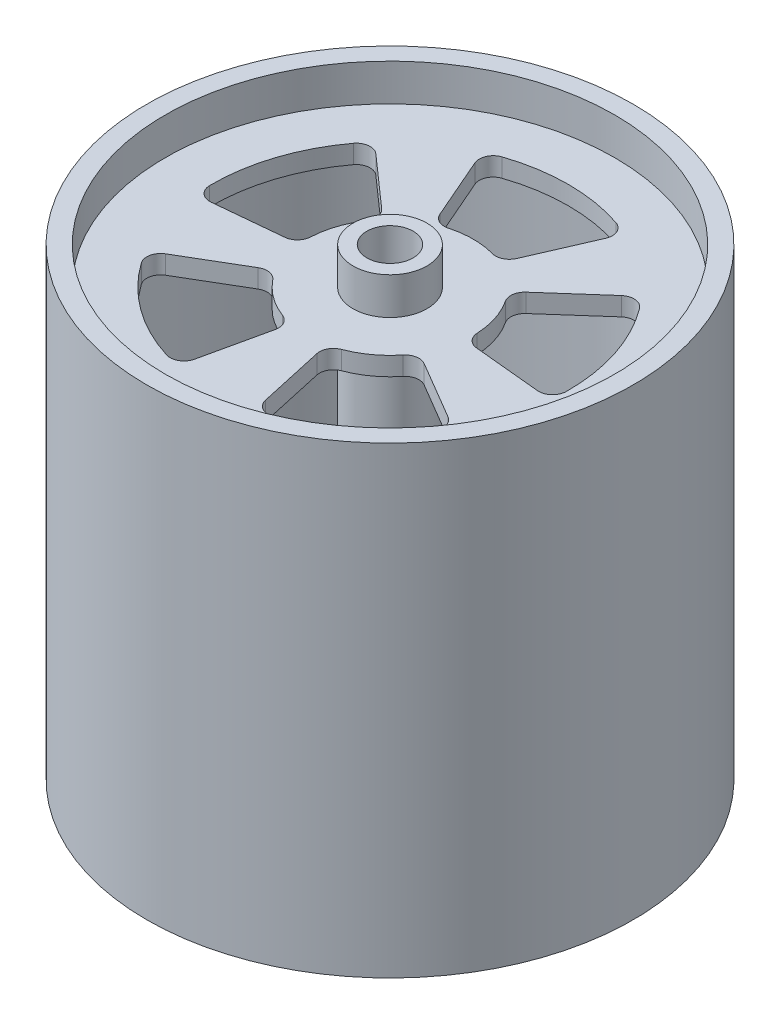
SolidWorks part; units mm, degrees
ref_plane "Front Plane" through (0, 0, 0) normal (0, 0, 1) x (1, 0, 0)
ref_plane "Top Plane" through (0, 0, 0) normal (0, 1, 0) x (1, 0, 0)
ref_plane "Right Plane" through (0, 0, 0) normal (1, 0, 0) x (0, 0, -1)
sketch "Sketch1" plane through (0, 0, 0) normal (0, 1, 0) x (1, 0, 0)
  circle A0 centre (0, 0) radius 52.5
  circle A1 centre (0, 0) radius 48.5
  dimension "D1" = 105
  dimension "D2" = 97
extrude "Boss-Extrude1" add sketch "Sketch1" along normal blind 100
sketch "Sketch2" plane through (0, 0, 0) normal (0, -1, 0) x (1, 0, 0)
  line L0 (7.6561, 34.5345) -> (4.4986, 20.2919)
  line L1 (7.6085, 2.4721) -> (46.1262, 14.9873)
  line L2 (0, 8) -> (0, 48.5)
  line L3 (30.4784, 17.9532) -> (17.9086, 10.549)
  line L4 (35.2102, 3.3904) -> (20.6889, 1.9921)
  line L5 (26.4928, -23.4389) -> (15.5668, -13.7723)
  line L6 (14.105, -32.4392) -> (8.2878, -19.0607)
  line L7 (-14.105, -32.4392) -> (-8.2878, -19.0607)
  line L8 (-26.4928, -23.4389) -> (-15.5668, -13.7723)
  line L9 (-35.2102, 3.3904) -> (-20.6889, 1.9921)
  line L10 (-30.4784, 17.9532) -> (-17.9086, 10.549)
  line L11 (-7.6561, 34.5345) -> (-4.4986, 20.2919)
  arc A0 (46.1262, 14.9873) -> (0, 48.5) centre (0, 0) ccw
  circle A1 centre (0, 0) radius 5
  circle A2 centre (0, 0) radius 8
  arc A3 (14.0452, 11.2576) -> (6.3664, 16.8365) centre (0, 0) ccw
  arc A4 (31.4028, 22.2737) -> (11.4795, 36.7488) centre (0, 0) ccw
  arc A5 (6.3664, 16.8365) -> (4.4986, 20.2919) centre (7.4275, 19.6426) cw
  arc A6 (17.9086, 10.549) -> (14.0452, 11.2576) centre (16.386, 13.1339) cw
  arc A7 (31.4028, 22.2737) -> (30.4784, 17.9532) centre (28.9558, 20.538) cw
  arc A8 (11.4795, 36.7488) -> (7.6561, 34.5345) centre (10.585, 33.8852) ccw
  arc A9 (38.4975, 0.4383) -> (35.2102, 3.3904) centre (35.4977, 0.4042) ccw
  arc A10 (30.8875, -22.9829) -> (38.4975, 0.4383) centre (0, 0) ccw
  arc A11 (30.8875, -22.9829) -> (26.4928, -23.4389) centre (28.4807, -21.192) cw
  arc A12 (15.5668, -13.7723) -> (15.0468, -9.8789) centre (17.5546, -11.5254) cw
  arc A13 (15.0468, -9.8789) -> (17.9798, -0.8521) centre (0, 0) ccw
  arc A14 (17.9798, -0.8521) -> (20.6889, 1.9921) centre (20.9765, -0.9941) cw
  arc A15 (12.3132, -36.4779) -> (14.105, -32.4392) centre (11.3538, -33.6354) ccw
  arc A16 (-12.3132, -36.4779) -> (12.3132, -36.4779) centre (0, 0) ccw
  arc A17 (-12.3132, -36.4779) -> (-14.105, -32.4392) centre (-11.3538, -33.6354) cw
  arc A18 (-8.2878, -19.0607) -> (-4.7457, -17.3631) centre (-5.5367, -20.257) cw
  arc A19 (-4.7457, -17.3631) -> (4.7457, -17.3631) centre (0, 0) ccw
  arc A20 (4.7457, -17.3631) -> (8.2878, -19.0607) centre (5.5367, -20.257) cw
  arc A21 (-30.8875, -22.9829) -> (-26.4928, -23.4389) centre (-28.4807, -21.192) ccw
  arc A22 (-38.4975, 0.4383) -> (-30.8875, -22.9829) centre (0, 0) ccw
  arc A23 (-38.4975, 0.4383) -> (-35.2102, 3.3904) centre (-35.4977, 0.4042) cw
  arc A24 (-20.6889, 1.9921) -> (-17.9798, -0.8521) centre (-20.9765, -0.9941) cw
  arc A25 (-17.9798, -0.8521) -> (-15.0468, -9.8789) centre (0, 0) ccw
  arc A26 (-15.0468, -9.8789) -> (-15.5668, -13.7723) centre (-17.5546, -11.5254) cw
  arc A27 (-31.4028, 22.2737) -> (-30.4784, 17.9532) centre (-28.9558, 20.538) ccw
  arc A28 (-11.4795, 36.7488) -> (-31.4028, 22.2737) centre (0, 0) ccw
  arc A29 (-11.4795, 36.7488) -> (-7.6561, 34.5345) centre (-10.585, 33.8852) cw
  arc A30 (-4.4986, 20.2919) -> (-6.3664, 16.8365) centre (-7.4275, 19.6426) cw
  arc A31 (-6.3664, 16.8365) -> (-14.0452, 11.2576) centre (0, 0) ccw
  arc A32 (-14.0452, 11.2576) -> (-17.9086, 10.549) centre (-16.386, 13.1339) cw
  point P71 (0, 0)
  circle M12 centre (0, 0) radius 48.5
  dimension "D1" = 97
  dimension "D2" = 10
  dimension "D3" = 3
  dimension "D6" = 10
  dimension "D7" = 10
  dimension "D10" = 3
  dimension "D4" = 72
  dimension "D5" = 72
  dimension "D8" = 12.5
  dimension "D9" = 12.5
  dimension "D11" = 5
extrude "Boss-Extrude2" add sketch "Sketch2" against normal blind 100 separate body contours A2 A1 region at (7.678, 0, 1.2161)
extrude "Boss-Extrude3" add sketch "Sketch2<3>" against normal blind 4 from offset 8 contours A2 L1 L2 A8 A4 A7 L3 A6 A3 A5 L0 M12 | A2 L2 L1 A13 A14 L4 A9 A10 A11 L5 A12 A19 A20 L6 A15 A16 A17 L7 A18 A25 A26 L8 A21 A22 A23 L9 A24 A31 A32 L10 A27 A28 A29 L11 A30 M12 region at (5.0853, 0, 6.9993) region at (-4.7092, 0, -6.4817) offset against normal yes
sketch "Sketch2<3>" plane through (0, 0, 0) normal (0, -1, 0) x (1, 0, 0) same geometry as "Sketch2"
extrude "Boss-Extrude4" add sketch "Sketch2<4>" against normal blind 4 from offset 88 contours A2 L2 L1 A13 A14 L4 A9 A10 A11 L5 A12 A19 A20 L6 A15 A16 A17 L7 A18 A25 A26 L8 A21 A22 A23 L9 A24 A31 A32 L10 A27 A28 A29 L11 A30 M12 | A2 L1 L2 A8 A4 A7 L3 A6 A3 A5 L0 M12 region at (5.0853, 0, 6.9993) region at (-4.7092, 0, -6.4817) offset against normal yes
sketch "Sketch2<4>" plane through (0, 0, 0) normal (0, -1, 0) x (1, 0, 0) same geometry as "Sketch2"
